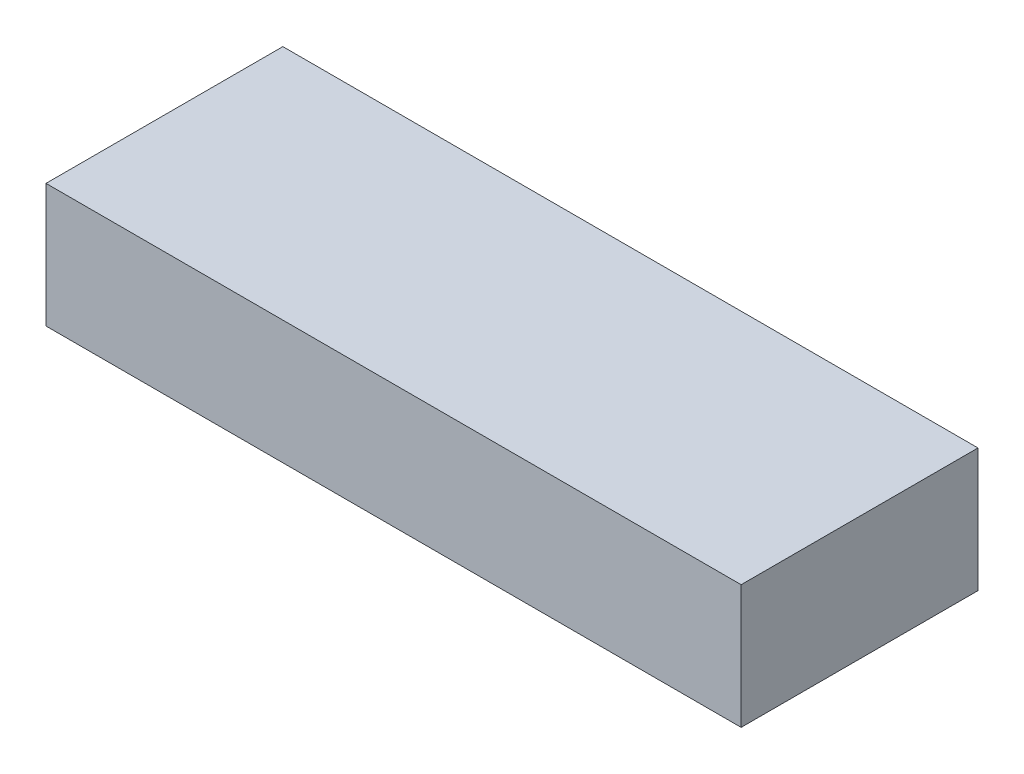
SolidWorks part; units mm, degrees
ref_plane "Front Plane" through (0, 0, 0) normal (0, 0, 1) x (1, 0, 0)
ref_plane "Top Plane" through (0, 0, 0) normal (0, 1, 0) x (1, 0, 0)
ref_plane "Right Plane" through (0, 0, 0) normal (1, 0, 0) x (0, 0, -1)
sketch "Sketch1" plane through (0, 0, 0) normal (0, 1, 0) x (1, 0, 0)
  line L1 (-67.5, -23) -> (67.5, -23)
  line L2 (-67.5, -23) -> (-67.5, 23)
  line L3 (-67.5, 23) -> (67.5, 23)
  line L4 (67.5, -23) -> (67.5, 23)
  line L5 (-67.5, -23) -> (67.5, 23) construction
  line L6 (-67.5, 23) -> (67.5, -23) construction
  point P0 (0, 0)
  dimension "D1" = 135
  dimension "D2" = 46
extrude "Boss-Extrude1" add sketch "Sketch1" along normal blind 24
